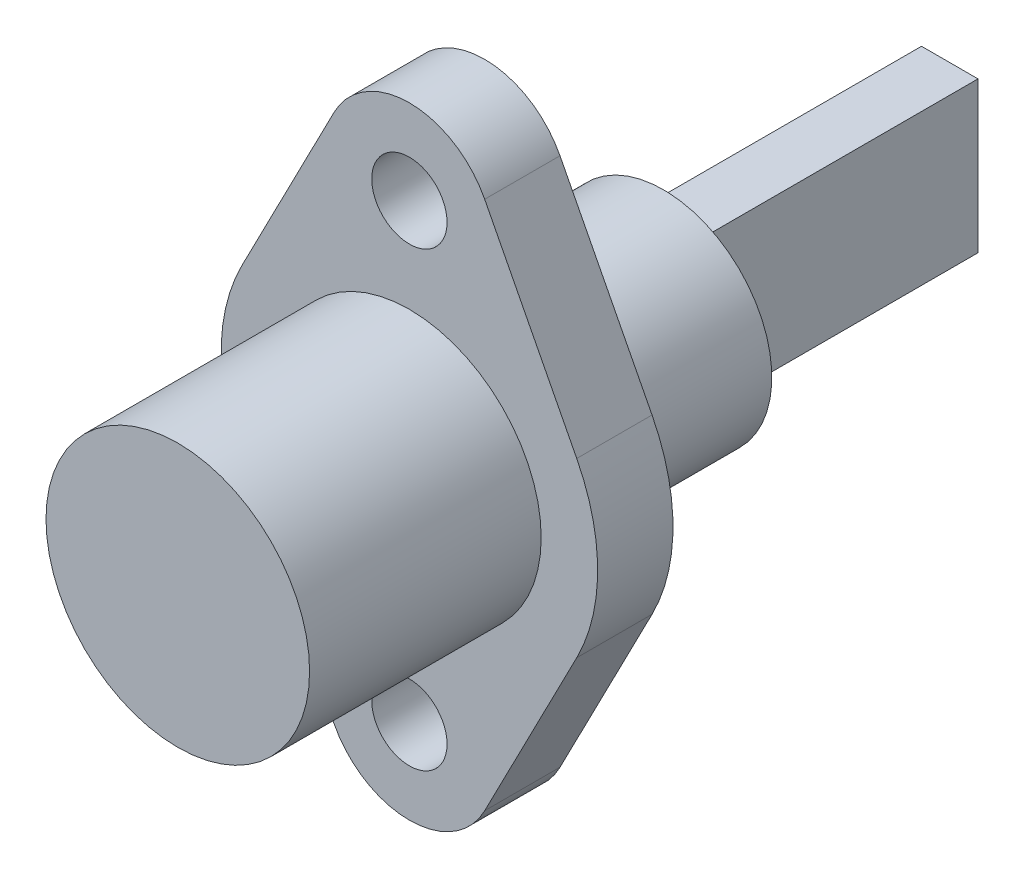
SolidWorks part; units mm, degrees
material "Custom Plastic"
ref_plane "X-Y Datum" through (0, 0, 0) normal (0, 0, 1) x (1, 0, 0)
ref_plane "X-Z Datum" through (0, 0, 0) normal (0, 1, 0) x (1, 0, 0)
ref_plane "Y-Z Datum" through (0, 0, 0) normal (1, 0, 0) x (0, 0, -1)
sketch "Sketch1" plane through (0, 0, 0) normal (0, 0, 1) x (1, 0, 0)
  line L0 (0, 17) -> (0, -17) construction
  line L1 (-10, 0) -> (10, 0) construction
  line L2 (-3.7696, 14.5084) -> (-8.8878, 4.5833)
  line L3 (3.7696, 14.5084) -> (8.8878, 4.5833)
  line L4 (3.7696, -14.5084) -> (8.8878, -4.5833)
  line L5 (-3.7696, -14.5084) -> (-8.8878, -4.5833)
  line L6 (0, 12) -> (0, -12) construction
  circle A0 centre (0, 0) radius 10
  circle A5 centre (0, 12) radius 2
  circle A6 centre (0, -12) radius 2
  circle A7 centre (0, 12) radius 4.5
  circle A8 centre (0, -12) radius 4.5
  point P4 (0, 0)
  point P8 (0, 0)
  point P26 (0, 0)
  dimension "D3" = 4
  dimension "D5" = 24
  dimension "D1" = 34
  dimension "D2" = 20
  dimension "D4" = 24
  dimension "D6" = 2.5
extrude "Boss-Extrude1" add sketch "Sketch1" along normal blind 4 contours A7 A0 A5 | A7 L2 A0 | A7 A0 L3 | A0 A8 A7 | A0 A7 | L5 A8 A0 | A8 A0 | A8 A0 A6 | A0 A8 L4 region at (-5.5325, 9.5178, 0) region at (0, 16.3849, 0) region at (0, 0, 0) region at (5.5325, 9.5178, 0) region at (0, 8.8462, 0) region at (-5.5325, -9.5178, 0) region at (-4.3707, -11.6473, 0) region at (0, -8.8462, 0) region at (5.5325, -9.5178, 0)
sketch "Sketch2" plane through (0, 0, 4) normal (0, 0, 1) x (1, 0, 0)
  circle A0 centre (0, 0) radius 7
  dimension "D1" = 14
extrude "Boss-Extrude2" add sketch "Sketch2" along normal blind 12.3
sketch "Sketch3" plane through (0, 0, 0) normal (0, 0, -1) x (-1, 0, 0)
  circle A0 centre (0, 0) radius 7.5
  dimension "D1" = 15
extrude "Boss-Extrude3" add sketch "Sketch3" along normal blind 0.5
sketch "Sketch4" plane through (0, 0, -0.5) normal (0, 0, -1) x (-1, 0, 0)
  line L1 (-1.5, 4) -> (1.5, 4)
  line L2 (-1.5, 4) -> (-1.5, -4)
  line L3 (-1.5, -4) -> (1.5, -4)
  line L4 (1.5, 4) -> (1.5, -4)
  line L5 (-1.5, 4) -> (1.5, -4) construction
  line L6 (-1.5, -4) -> (1.5, 4) construction
  point P0 (0, 0)
  dimension "D1" = 8
  dimension "D2" = 3
extrude "Boss-Extrude4" add sketch "Sketch4" along normal blind 24.2
sketch "Sketch5" plane through (0, 0, -0.5) normal (0, 0, -1) x (-1, 0, 0)
  circle A0 centre (0, 0) radius 5.75
  dimension "D1" = 11.5
extrude "Boss-Extrude5" add sketch "Sketch5" along normal blind 9
